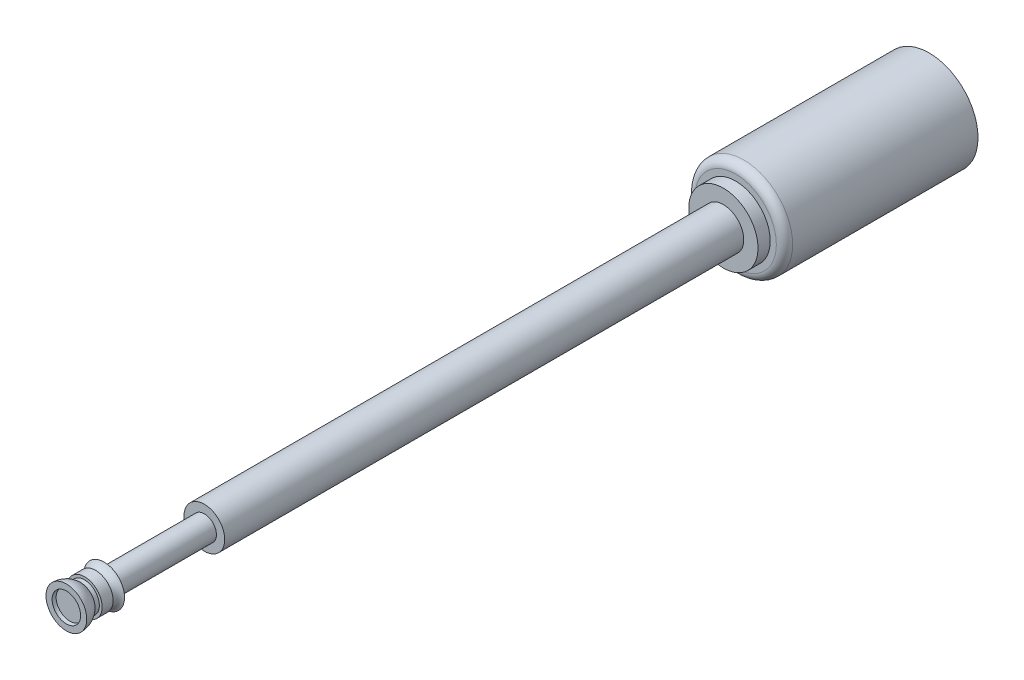
SolidWorks part; units mm, degrees
ref_plane "Front Plane" through (0, 0, 0) normal (0, 0, 1) x (1, 0, 0)
ref_plane "Top Plane" through (0, 0, 0) normal (0, 1, 0) x (1, 0, 0)
ref_plane "Right Plane" through (0, 0, 0) normal (1, 0, 0) x (0, 0, -1)
sketch "Sketch1" plane through (0, 0, 0) normal (0, 0, 1) x (1, 0, 0)
  circle A0 centre (0, 0) radius 12.7
  circle A1 centre (0, 0) radius 30.48
  dimension "D1" = 25.4
  dimension "D2" = 60.96
extrude "Boss-Extrude1" add sketch "Sketch1" along normal blind 393.7 contours A0 region at (0, 0, 0)
extrude "Boss-Extrude2" add sketch "Sketch1<3>" against normal blind 120.65 separate body contours A1 A0 region at (-29.6179, 0, 0)
sketch "Sketch1<3>" plane through (0, 0, 0) normal (0, 0, 1) x (1, 0, 0) same geometry as "Sketch1"
fillet "Fillet1" radius 5.08 1 edges at (30.48, 0, 0)
sketch "Sketch2" plane through (0, 0, 0) normal (0, 0, 1) x (1, 0, 0)
  circle A0 centre (0, 0) radius 21.59
  dimension "D1" = 43.18
extrude "Boss-Extrude3" add sketch "Sketch2" along normal blind 7.62
sketch "Sketch3" plane through (0, 0, 0) normal (0, 1, 0) x (1, 0, 0)
  line L0 (12.7, -393.7) -> (0, -393.7)
  line L1 (-12.7, -393.7) -> (12.7, -393.7) construction
  line L2 (0, -393.7) -> (0, -408.3685)
  line L3 (8.89, -417.2585) -> (12.7, -417.2585)
  line L4 (9.2478, -408.554) -> (9.2478, -405.9355)
  line L5 (9.2478, -405.9355) -> (10.9476, -405.9355)
  line L6 (10.9476, -405.9355) -> (10.9476, -399.0592)
  line L7 (10.9476, -399.0592) -> (9.1705, -399.0592)
  arc A0 (0, -408.3685) -> (8.89, -417.2585) centre (0, -417.2585) cw
  arc A1 (12.7, -417.2585) -> (9.2478, -408.554) centre (0, -417.2585) ccw
  arc A4 (9.1705, -399.0592) -> (12.7, -393.7) centre (15.004, -399.0592) cw
  dimension "D2" = 8.89
  dimension "D3" = 12.7
  dimension "D1" = 23.5585
revolve "Revolve2" add sketch "Sketch3" angle 360 about L2
sketch "Sketch4" plane through (0, 0, 0) normal (0, 1, 0) x (1, 0, 0)
  line L0 (0, -393.7) -> (0, -417.2585) construction
  line L1 (12.7, -393.7) -> (-12.7, -393.7) construction
  line L2 (-12.7, -417.2585) -> (12.7, -417.2585) construction
  line L4 (-11.4554, -413.5483) -> (0, -413.5483)
  line L5 (-11.4554, -413.5483) -> (-11.4554, -415.036)
  line L6 (-11.4554, -415.036) -> (0, -415.036)
  line L7 (0, -413.5483) -> (0, -415.036)
  line L8 (-11.4554, -413.5483) -> (0, -415.036) construction
  line L9 (-11.4554, -415.036) -> (0, -413.5483) construction
  point P6 (-5.7277, -414.2921)
  dimension "D1" = 21.336
revolve "Revolve3" add sketch "Sketch4" angle 360 about L0 reverse direction yes
sketch "Sketch5" plane through (0, 0, 0) normal (0, 1, 0) x (1, 0, 0)
  line L0 (12.7, -393.7) -> (-12.7, -393.7) construction
  line L1 (-26.9316, -331.216) -> (-7.5235, -331.216)
  line L2 (-26.9316, -331.216) -> (-26.9316, -393.7)
  line L3 (-26.9316, -393.7) -> (-7.5235, -393.7)
  line L4 (-7.5235, -331.216) -> (-7.5235, -393.7)
  line L5 (-26.9316, -331.216) -> (-7.5235, -393.7) construction
  line L6 (-26.9316, -393.7) -> (-7.5235, -331.216) construction
  line L7 (0, -417.2585) -> (0, -393.7) construction
  line L8 (-12.7, -417.2585) -> (12.7, -417.2585) construction
  point P0 (-17.2275, -362.458)
  dimension "D1" = 62.484
  dimension "D2" = 7.5235
revolve "Cut-Revolve1" cut sketch "Sketch5" angle 360 about L7
sketch "Sketch6" plane through (0, 0, -120.65) normal (0, 0, -1) x (-1, 0, 0)
  point P0 (0, 0)
